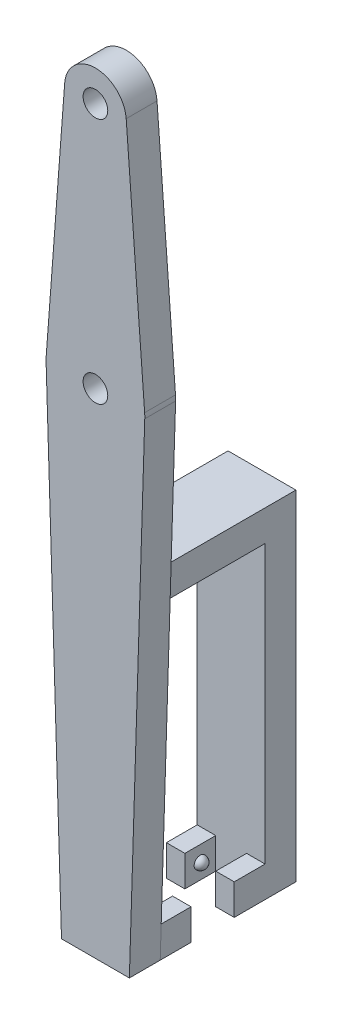
SolidWorks part; units mm, degrees
note: The reader was unsure of these and kept them because the rebuilt part matched: shared geometry of "Sketch2<3>".
ref_plane "Front Plane" through (0, 0, 0) normal (0, 0, 1) x (1, 0, 0)
ref_plane "Top Plane" through (0, 0, 0) normal (0, 1, 0) x (1, 0, 0)
ref_plane "Right Plane" through (0, 0, 0) normal (1, 0, 0) x (0, 0, -1)
sketch "Sketch1" plane through (0, 0, 0) normal (0, 0, 1) x (1, 0, 0)
  line L0 (0, 62.5) -> (0, -62.5) construction
  line L1 (-5.5, 62.5) -> (5.5, 62.5) construction
  line L2 (-5.5, 62.5) -> (-5.5, -62.5) construction
  line L3 (-5.5, -62.5) -> (5.5, -62.5) construction
  line L4 (5.5, 62.5) -> (5.5, -62.5) construction
  line L5 (-5.5, 62.5) -> (5.5, -62.5) construction
  line L6 (-5.5, -62.5) -> (5.5, 62.5) construction
  line L7 (-4.9859, 57.875) -> (-7.9775, 18.1)
  line L8 (-7.9961, 17.2497) -> (-5.5, -62.5)
  line L9 (-5.5, -62.5) -> (5.5, -62.5)
  line L10 (5.5, -62.5) -> (7.9961, 17.2497)
  line L11 (4.9859, 57.875) -> (7.9775, 18.1)
  circle A0 centre (0, 17.5) radius 2
  circle A1 centre (0, 57.5) radius 2
  circle A2 centre (0, 57.5) radius 5
  circle A3 centre (0, 17.5) radius 8
  point P0 (0, 0)
  dimension "D2" = 4
  dimension "D4" = 4
  dimension "D1" = 5
  dimension "D3" = 11
  dimension "D5" = 40
  dimension "D6" = 80
  dimension "D7" = 3
  dimension "D8" = 6
extrude "Boss-Extrude1" add sketch "Sketch1" along normal blind 5
sketch "Sketch2" plane through (0, 0, 0) normal (0, 0, -1) x (-1, 0, 0)
  line L0 (0, -62.5) -> (0, 62.5) construction
  line L1 (5.5, -62.5) -> (-5.5, -62.5) construction
  line L3 (-5.5, -62.5) -> (5.5, -62.5)
  line L4 (-5.5, -62.5) -> (-5.5, -57.5)
  line L5 (-5.5, -57.5) -> (5.5, -57.5)
  line L6 (5.5, -62.5) -> (5.5, -57.5)
  line L8 (-5.5, -12.5) -> (5.5, -12.5)
  line L9 (-5.5, -12.5) -> (-5.5, -7.5)
  line L10 (-5.5, -7.5) -> (5.5, -7.5)
  line L11 (5.5, -12.5) -> (5.5, -7.5)
  arc A0 (4.9859, 57.875) -> (-4.9859, 57.875) centre (0, 57.5) ccw construction
  point P12 (4.5551, -57.5)
  point P13 (0, 0)
  point P18 (0, -12.5)
  point P19 (5.5, -62.5)
  point P21 (4.4233, -62.5)
  dimension "D1" = 5
  dimension "D2" = 50
  dimension "D3" = 5
  dimension "D4" = 11
extrude "Boss-Extrude2" add sketch "Sketch2" along normal blind 5
extrude "Boss-Extrude3" add sketch "Sketch2<3>" along normal blind 22 contours L8 L0 L10 L9 | L0 L8 L11 L10
sketch "Sketch2<3>" plane through (0, 0, 0) normal (0, 0, -1) x (-1, 0, 0) same geometry as "Sketch2"
sketch "Sketch4" plane through (0, -57.5, 0) normal (0, 1, 0) x (1, 0, 0)
  line L0 (5.5, 0) -> (-5.5, 0) construction
  line L1 (2.5, 0) -> (-2.5, 0)
  line L2 (2.5, 0) -> (2.5, 5)
  line L3 (2.5, 5) -> (-2.5, 5)
  line L4 (-2.5, 0) -> (-2.5, 5)
  line L5 (5.5, 5) -> (-5.5, 5) construction
  line L6 (5.5, 5) -> (5.5, 0) construction
  line L8 (-5.5, 5) -> (-5.5, 0) construction
  point P8 (2.4937, -1.4583)
  dimension "D1" = 3
  dimension "D2" = 3
extrude "Cut-Extrude1" cut sketch "Sketch4" against normal blind 20
sketch "Sketch5" plane through (2.5, 0, 0) normal (-1, 0, 0) x (0, 0, 1)
  line L0 (0, -60) -> (-5, -60) construction
  line L1 (0, -62.5) -> (0, -57.5) construction
  line L2 (-5, -57.5) -> (-5, -62.5) construction
  line L3 (-3.5, -60) -> (-1.5, -60)
  arc A0 (-3.5, -60) -> (-1.5, -60) centre (-2.5, -60) ccw
  dimension "D1" = 1
revolve "Revolve1" add sketch "Sketch5" angle 360 about L0
mirror "Mirror1" about plane through (0, 0, 0) normal (1, 0, 0) of "Revolve1"
sketch "Sketch6" plane through (0, -12.5, 0) normal (0, -1, 0) x (-1, 0, 0)
  line L0 (5.5, 22) -> (5.5, 0) construction
  line L1 (-5.5, 22) -> (5.5, 22)
  line L2 (-5.5, 22) -> (-5.5, 17)
  line L3 (-5.5, 17) -> (5.5, 17)
  line L4 (5.5, 22) -> (5.5, 17)
  point P7 (1.4279, 15.3231)
  dimension "D1" = 5
extrude "Boss-Extrude4" add sketch "Sketch6" along normal up to surface (50 mm away) up to face at (0, -62.5, -1)
ref_plane "Plane1" through (0, 0, -8.5) normal (0, 0, -1) x (-1, 0, 0)
mirror "Mirror2" about plane through (0, 0, -8.5) normal (0, 0, -1) of "Cut-Extrude1", "Boss-Extrude2", "Mirror1", "Revolve1"
